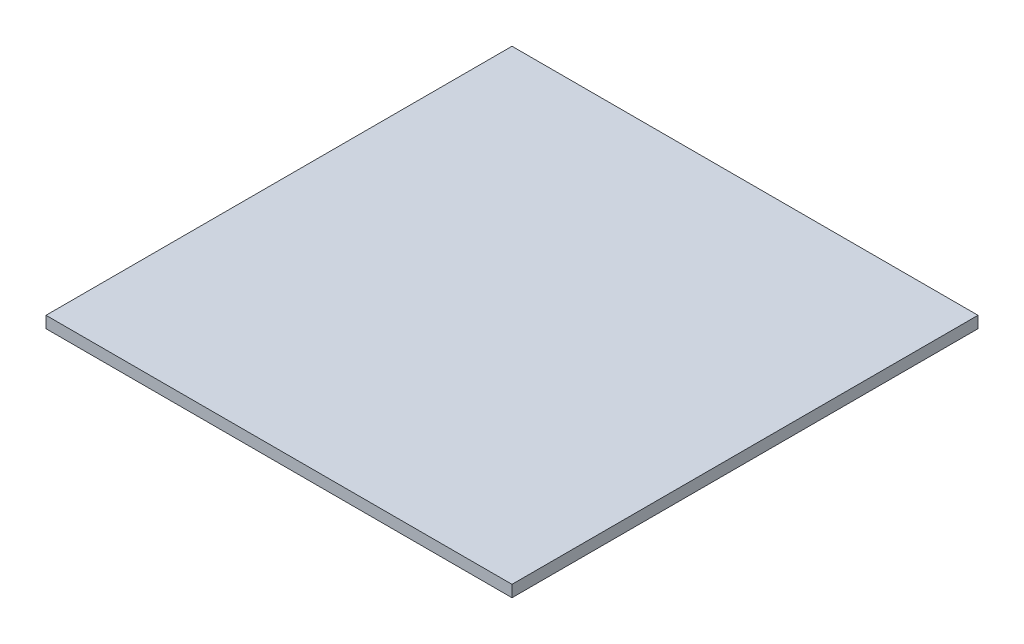
SolidWorks part; units mm, degrees
ref_plane "Front Plane" through (0, 0, 0) normal (0, 0, 1) x (1, 0, 0)
ref_plane "Top Plane" through (0, 0, 0) normal (0, 1, 0) x (1, 0, 0)
ref_plane "Right Plane" through (0, 0, 0) normal (1, 0, 0) x (0, 0, -1)
sketch "Sketch1" plane through (0, 0, 0) normal (0, 1, 0) x (1, 0, 0)
  line L0 (0, 0) -> (254, 0)
  line L1 (254, 0) -> (254, 254)
  line L2 (254, 254) -> (0, 254)
  line L3 (0, 254) -> (0, 0)
  dimension "D1" = 254
  dimension "D2" = 254
extrude "Boss-Extrude1" add sketch "Sketch1" along normal blind 6.35
equation "\"wall_thickness\" = 0.125in"
equation "\"base_thickness\" = 0.25in"
equation "\"D1@Boss-Extrude1\"=\"base_thickness\""
